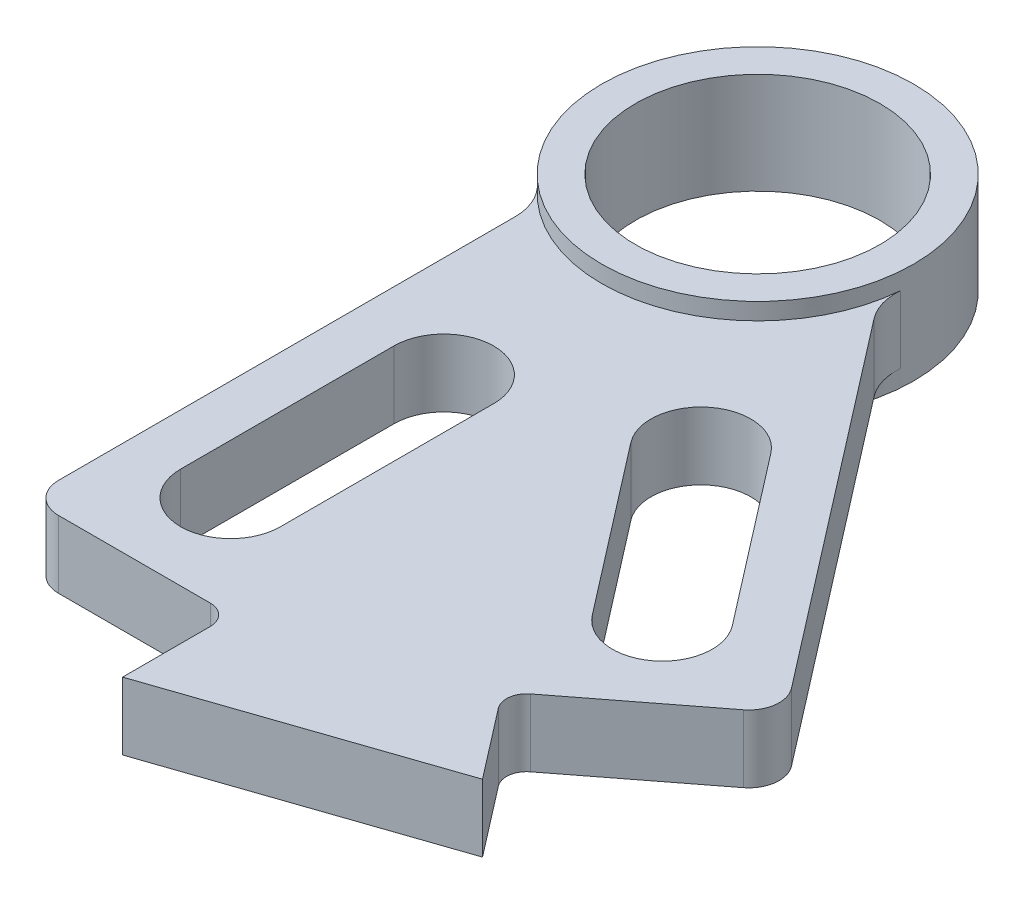
SolidWorks part; units mm, degrees
material "AISI 4130 Steel, normalized at 870C"
ref_plane "Front Plane" through (0, 0, 0) normal (0, 0, 1) x (1, 0, 0)
ref_plane "Top Plane" through (0, 0, 0) normal (0, 1, 0) x (1, 0, 0)
ref_plane "Right Plane" through (0, 0, 0) normal (1, 0, 0) x (0, 0, -1)
sketch "Sketch1" plane through (0, 0, 0) normal (0, 1, 0) x (1, 0, 0)
  line L0 (0, -54.3052) -> (0, -14.6812) construction
  line L1 (33.1712, -42.9969) -> (8.9677, -11.624) construction
  line L2 (0, -49.6062) -> (0, -29.5402) construction
  line L5 (-4.699, -49.6062) -> (-4.699, -29.5402)
  line L8 (-9.525, -59.1312) -> (9.525, -59.1312)
  line L9 (28.5775, -52.636) -> (43.6606, -40.9998)
  line L10 (-9.525, -59.1312) -> (-9.525, -11.1719)
  line L11 (43.6606, -40.9998) -> (14.3657, -3.0274)
  line L12 (9.525, -59.1312) -> (9.525, -69.2912)
  line L13 (28.5775, -52.636) -> (34.7835, -60.6804)
  line L14 (9.525, -69.2912) -> (34.7835, -60.6804)
  line L15 (0, -14.6812) -> (0, 0) construction
  line L16 (0, -59.1312) -> (0, -54.3052) construction
  line L17 (36.119, -46.8179) -> (33.1712, -42.9969)
  line L18 (4.699, -49.6062) -> (4.699, -29.5402)
  line L19 (18.044, -23.3888) -> (30.3009, -39.2764) construction
  line L20 (21.7645, -20.5186) -> (34.0214, -36.4061)
  line L21 (14.3235, -26.2591) -> (26.5804, -42.1466)
  line L22 (8.9677, -11.624) -> (0, 0) construction
  line L23 (0, 0) -> (17.6212, -51.6889) construction
  line L25 (202.9905, -263.1188) -> (17.0665, -22.1219) construction
  line L27 (0, 0) -> (22.1542, -64.9858) construction
  circle A0 centre (0, 0) radius 11.5062
  circle A1 centre (0, 0) radius 14.6812
  arc A2 (-4.699, -49.6062) -> (4.699, -49.6062) centre (0, -49.6062) ccw
  arc A3 (4.699, -29.5402) -> (-4.699, -29.5402) centre (0, -29.5402) ccw
  arc A4 (21.7645, -20.5186) -> (14.3235, -26.2591) centre (18.044, -23.3888) ccw
  arc A5 (26.5804, -42.1466) -> (34.0214, -36.4061) centre (30.3009, -39.2764) ccw
  point P9 (0, -39.5732)
  point P14 (24.1724, -31.3326)
  point P23 (0, -59.1312)
  point P26 (36.119, -46.8179)
  point P33 (0, -54.3052)
  point P36 (33.1712, -42.9969)
  point P38 (0, -24.8412)
  dimension "D2" = 29.3624
  dimension "D3" = 44.45
  dimension "D4" = 4.826
  dimension "D6" = 10.16
  dimension "D5" = 4.826
  dimension "D8" = 10.16
  dimension "D9" = 54.61
  dimension "D7" = 19.05
extrude "Bearing extrude" add sketch "Sketch1" along normal mid plane 9.525 contours A1 A0 region at (-5.9782, 0, -12.9529)
extrude "Boss-Extrude2" add sketch "Sketch1<5>" along normal mid plane 6.35 contours A1 L10 L8 L12 L14 L13 L9 L11 A4 A2 region at (13.1696, 0, 38.6307)
sketch "Sketch1<5>" plane through (0, 0, 0) normal (0, 1, 0) x (1, 0, 0) same geometry as "Sketch1"
sketch3d "Tab Point"
  line L0 (17.6212, 0, 51.6889) -> (17.6212, 22.225, 51.6889) construction
  line L1 (0, 0, 0) -> (17.6212, 0, 51.6889) construction
  line L2 (0, 0, 0) -> (22.1542, 0, 64.9858) construction
  dimension "D1" = 22.225
fillet "Fillet1" radius 5.08 2 edges at (14.3657, 0, 3.0274) (-9.525, 0, 11.1719)
fillet "Fillet2" radius 1.905 2 edges at (28.5775, 0, 52.636) (9.525, 0, 59.1312)
fillet "Fillet3" radius 2.8575 2 edges at (43.6606, 0, 40.9998) (-9.525, 0, 59.1312)
equation "\"Apex_thickness\"= .25"
equation "\"Bearing_diameter\"= .906"
equation "\"A-arm_angle\"= 32.91"
equation "\"D1@Sketch1\"=\"Bearing_diameter\""
equation "\"D1@Boss-Extrude2\"= \"Apex_thickness\""
equation "\"apex slot\"= 1.4"
equation "\"tube diameter\"= 5 / 8"
